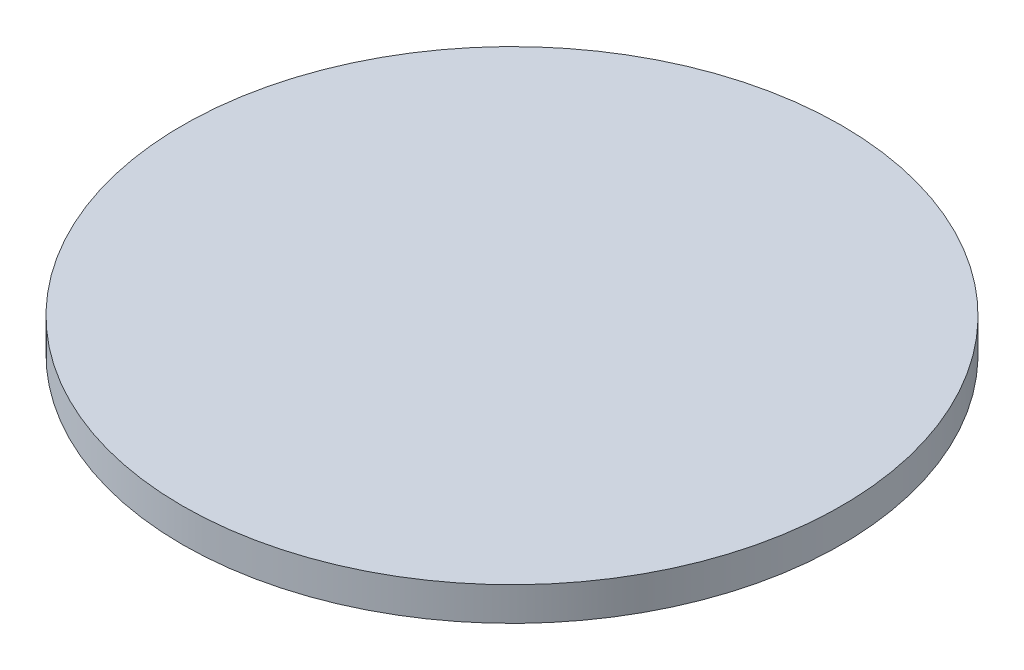
SolidWorks part; units mm, degrees
ref_plane "Ebene vorne" through (0, 0, 0) normal (0, 0, 1) x (1, 0, 0)
ref_plane "Ebene oben" through (0, 0, 0) normal (0, 1, 0) x (1, 0, 0)
ref_plane "Ebene rechts" through (0, 0, 0) normal (1, 0, 0) x (0, 0, -1)
sketch "Skizze1" plane through (0, 0, 0) normal (0, 1, 0) x (1, 0, 0)
  circle A0 centre (0, 0) radius 59
  circle A1 centre (0, 0) radius 6
  dimension "D1" = 118
  dimension "D2" = 12
extrude "Aufsatz-Linear austragen1" add sketch "Skizze1" along normal blind 6 contours A0
extrude "Aufsatz-Linear austragen2" add sketch "Skizze1<3>" against normal blind 2 draft 30 contours A1 region at (0, 0, 0)
sketch "Skizze1<3>" plane through (0, 0, 0) normal (0, 1, 0) x (1, 0, 0) same geometry as "Skizze1"
sketch "Skizze2" plane through (0, -2, 0) normal (0, -1, 0) x (1, 0, 0)
  circle A0 centre (0, 0) radius 4.2628
extrude "Schnitt-Linear austragen1" cut sketch "Skizze2" against normal blind 0.5 draft 45
